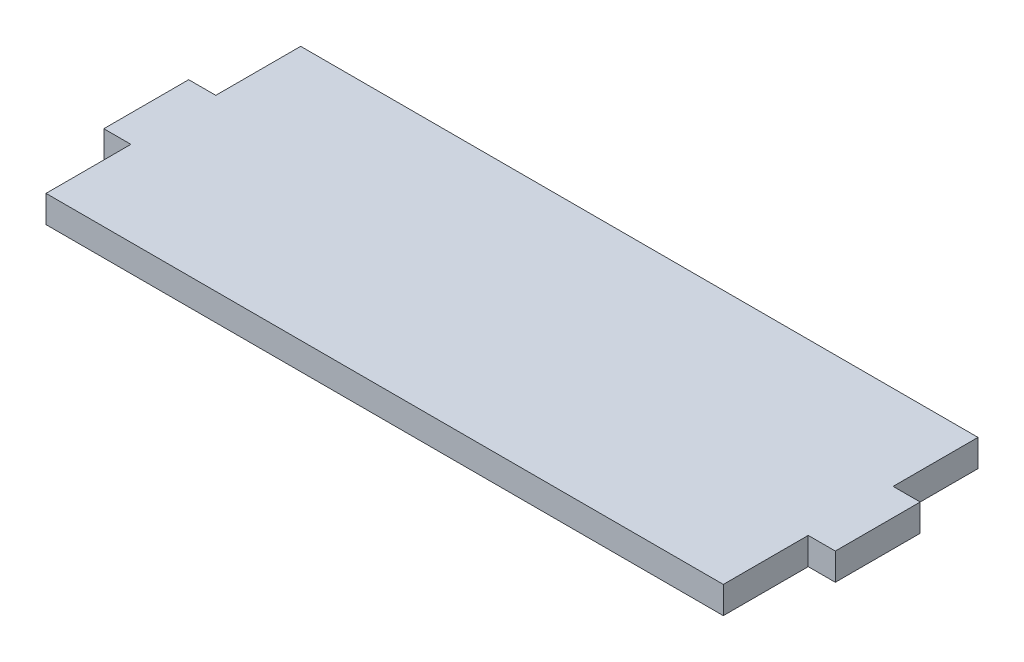
SolidWorks part; units mm, degrees
ref_plane "Front Plane" through (0, 0, 0) normal (0, 0, 1) x (1, 0, 0)
ref_plane "Top Plane" through (0, 0, 0) normal (0, 1, 0) x (1, 0, 0)
ref_plane "Right Plane" through (0, 0, 0) normal (1, 0, 0) x (0, 0, -1)
sketch "Sketch1" plane through (0, 0, 0) normal (0, 1, 0) x (1, 0, 0)
  line L1 (-81, 28.2) -> (81, 28.2)
  line L2 (-81, 28.2) -> (-81, -28.2)
  line L3 (-81, -28.2) -> (81, -28.2)
  line L4 (81, 28.2) -> (81, -28.2)
  line L5 (-81, 28.2) -> (81, -28.2) construction
  line L6 (-81, -28.2) -> (81, 28.2) construction
  line L7 (-81, 28.2) -> (-75, 28.2)
  line L8 (-81, 28.2) -> (-81, 9.4)
  line L9 (-81, 9.4) -> (-75, 9.4)
  line L10 (-75, 28.2) -> (-75, 9.4)
  line L11 (-75, 9.4) -> (-81, 9.4)
  line L12 (-75, 9.4) -> (-75, -9.4)
  line L13 (-75, -9.4) -> (-81, -9.4)
  line L14 (-81, 9.4) -> (-81, -9.4)
  line L15 (-81, -9.4) -> (-75, -9.4)
  line L16 (-81, -9.4) -> (-81, -28.2)
  line L17 (-81, -28.2) -> (-75, -28.2)
  line L18 (-75, -9.4) -> (-75, -28.2)
  point P0 (0, 0)
  dimension "D2" = 56.4
  dimension "D1" = 162
  dimension "D3" = 6
sketch "Sketch2" plane through (0, 0, 0) normal (0, 0, 1) x (1, 0, 0)
  line L0 (0, 0) -> (0, 6) construction
  line L1 (-81, 0) -> (81, 0) construction
extrude "Boss-Extrude1" add sketch "Sketch1" along normal up to vertex (6 mm away) contours L2 L3 L4 L1 up to point (0, 6, 0)
extrude "Cut-Extrude1" cut sketch "Sketch1<3>" along normal through all contours L18 L13 L2 L3 | L10 L1 L2 L9 region at (-78, 0, -18.8) region at (-78, 0, 18.8)
sketch "Sketch1<3>" plane through (0, 0, 0) normal (0, 1, 0) x (1, 0, 0) same geometry as "Sketch1"
mirror "Mirror1" about plane through (0, 0, 0) normal (1, 0, 0) of "Cut-Extrude1"
equation "\"glass_width\" = 150"
equation "\"glass_height\"= 100"
equation "\"glass_thickness\"= 4"
equation "\"brood_space\"= 42"
equation "\"t1\"= 6"
equation "\"t2\"= 3.2"
equation "\"box_depth\"= \"brood_space\" + \"glass_thickness\" + \"glass_thickness\" + \"t2\" + \"t2\""
equation "\"box_width\"= \"glass_width\" + \"t1\" + \"t1\""
equation "\"food_height\"= 70"
equation "\"box_height\" = \"glass_height\" + ( \"t1\" * 3 ) + \"food_height\""
equation "\"D1@Sketch2\"=\"t1\""
equation "\"D2@Sketch1\"=\"box_depth\""
equation "\"D1@Sketch1\"=\"box_width\""
equation "\"D3@Sketch1\"=\"t1\""
